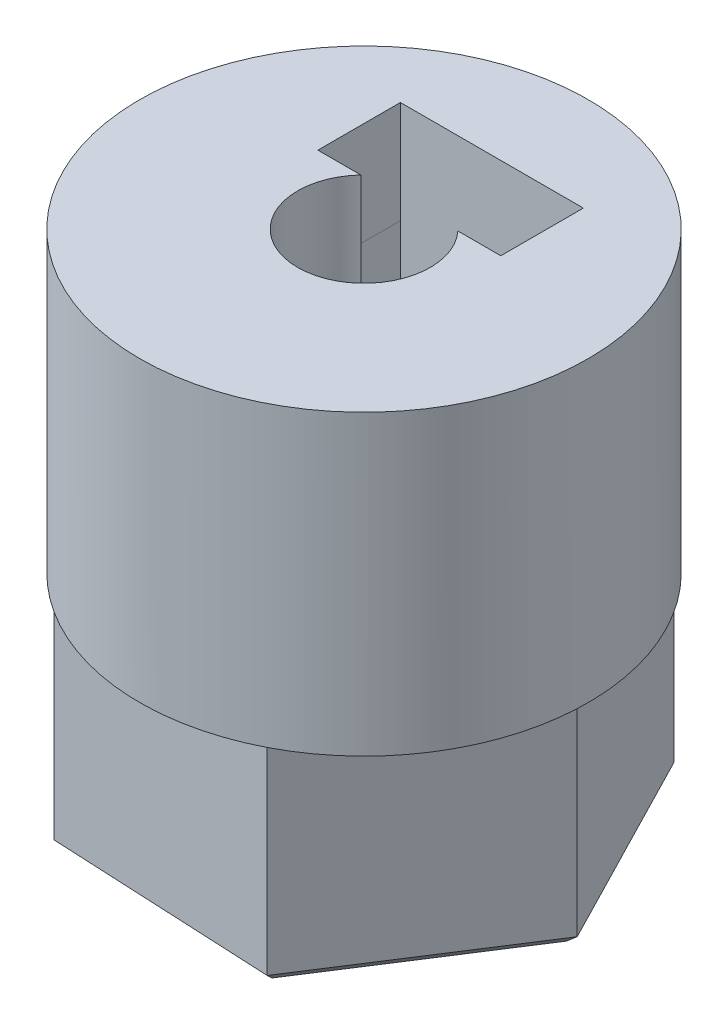
SolidWorks part; units mm, degrees
ref_plane "Front Plane" through (0, 0, 0) normal (0, 0, 1) x (1, 0, 0)
ref_plane "Top Plane" through (0, 0, 0) normal (0, 1, 0) x (1, 0, 0)
ref_plane "Right Plane" through (0, 0, 0) normal (1, 0, 0) x (0, 0, -1)
sketch "Sketch1" plane through (0, 0, 0) normal (0, 1, 0) x (1, 0, 0)
  line L1 (3.1706, -6.1601) -> (6.9201, -0.3342)
  line L2 (6.9201, -0.3342) -> (3.7495, 5.8259)
  line L3 (3.7495, 5.8259) -> (-3.1706, 6.1601)
  line L4 (-3.1706, 6.1601) -> (-6.9201, 0.3342)
  line L5 (-6.9201, 0.3342) -> (-3.7495, -5.8259)
  line L6 (-3.7495, -5.8259) -> (3.1706, -6.1601)
  circle A0 centre (0, 0) radius 6 construction
extrude "Boss-Extrude1" add sketch "Sketch1" along normal blind 6.4
sketch "Sketch2" plane through (0, 6.4, 0) normal (0, 1, 0) x (1, 0, 0)
  circle A0 centre (0, 0) radius 6.9282
extrude "Boss-Extrude2" add sketch "Sketch2" along normal blind 9.2
sketch "Sketch3" plane through (0, 15.6, 0) normal (0, 1, 0) x (1, 0, 0)
  circle A0 centre (0, 0) radius 1.65
  circle A1 centre (0, 0) radius 6.9282
  circle A2 centre (0, 0) radius 6.9282
  circle A3 centre (0, 0) radius 2.05
  dimension "D2" = 3.3
  dimension "D3" = 4.1
  dimension "D1" = 0
extrude "Cut-Extrude3" cut sketch "Sketch3" against normal through all contours A0
sketch "Sketch4" plane through (0, 15.6, 0) normal (0, 1, 0) x (1, 0, 0)
  line L0 (0, 0) -> (0, 4.5251) construction
  line L2 (2.825, 1.4) -> (-2.825, 1.4)
  line L3 (2.825, 1.4) -> (2.825, 3.95)
  line L4 (2.825, 3.95) -> (-2.825, 3.95)
  line L5 (-2.825, 1.4) -> (-2.825, 3.95)
  dimension "D2" = 5.65
  dimension "D3" = 2.55
extrude "Cut-Extrude4" cut sketch "Sketch4" against normal blind 6.4
sketch "Sketch5" plane through (0, 0, -3.95) normal (0, 0, 1) x (1, 0, 0)
  line L0 (0, 15.6) -> (0, 10.8)
  line L1 (2.825, 15.6) -> (-2.825, 15.6) construction
  circle A0 centre (0, 10.8) radius 1.5
  dimension "D2" = 3
  dimension "D1" = 4.8
extrude "Cut-Extrude5" cut sketch "Sketch5" against normal up to next and the other way up to next contours A0 region at (-1.0307, 9.7693, -3.95)
sketch "Sketch7" plane through (0, 0, -3.95) normal (0, 0, 1) x (1, 0, 0)
  line L1 (-2.825, 12.4378) -> (-2.8309, 9.1724)
  line L2 (-2.8309, 9.1724) -> (-0.0059, 7.5346)
  line L3 (-0.0059, 7.5346) -> (2.825, 9.1622)
  line L4 (2.825, 9.1622) -> (2.8309, 12.4276)
  line L5 (2.8309, 12.4276) -> (0.0059, 14.0654)
  line L6 (0.0059, 14.0654) -> (-2.825, 12.4378)
  circle A0 centre (0, 10.8) radius 2.8279 construction
extrude "Cut-Extrude7" cut sketch "Sketch7" along normal blind 2.55
extrude "Cut-Extrude8" cut sketch "Sketch3<4>" against normal blind 9.4 contours A3 A0 region at (-1.992, 15.6, 0)
sketch "Sketch3<4>" plane through (0, 15.6, 0) normal (0, 1, 0) x (1, 0, 0) same geometry as "Sketch3"
chamfer "Chamfer1" distance 0.3 angle 45 7 edges at (5.0454, 0, 3.2472) (5.3348, 0, -2.7459) (0.2894, 0, -5.993) (-5.0454, 0, -3.2472) (-5.3348, 0, 2.7459) (-0.2894, 0, 5.993) (0, 0, 1.65)
